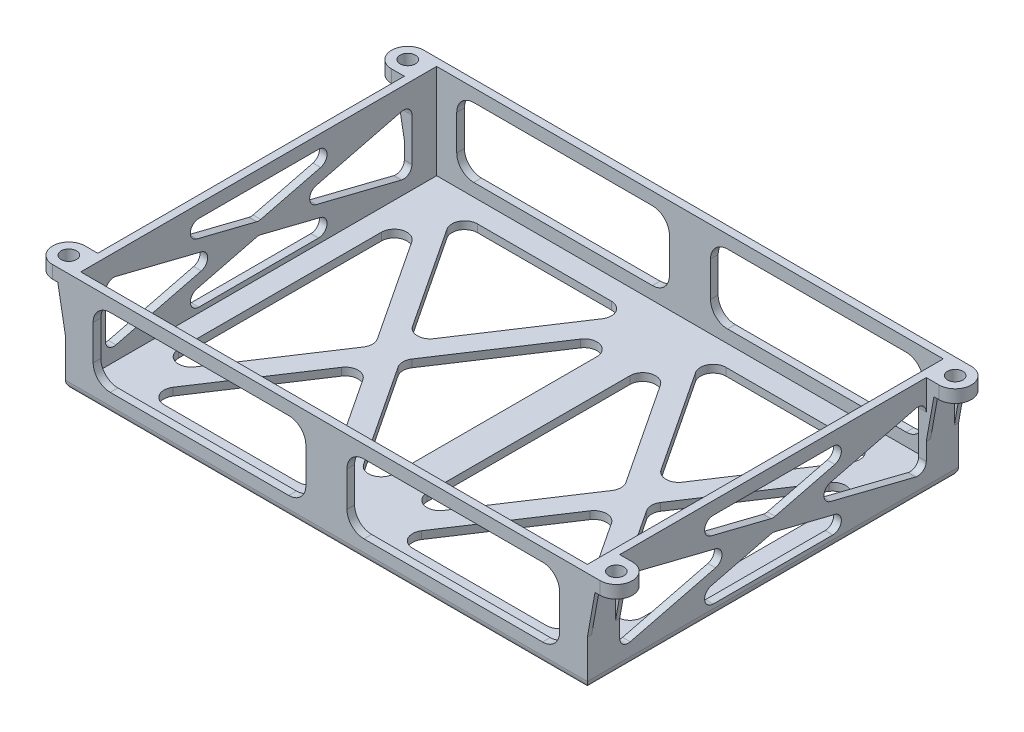
SolidWorks part; units mm, degrees
other "Markup2"
sketch "Sketch32" plane through (-159.4724, 0, 108) normal (-0.262, -0.0774, 0.962) x (0.8638, -0.4632, 0.198)
ref_plane "Front Plane" through (0, 0, 0) normal (0, 0, 1) x (1, 0, 0)
ref_plane "Top Plane" through (0, 0, 0) normal (0, 1, 0) x (1, 0, 0)
ref_plane "Right Plane" through (0, 0, 0) normal (1, 0, 0) x (0, 0, -1)
sketch "Sketch1" plane through (0, 0, 0) normal (0, 1, 0) x (1, 0, 0)
  line L0 (-2.286, -2.286) -> (-2.286, -108.556) construction
  line L1 (0, 0) -> (-155.842, 0)
  line L2 (0, 0) -> (0, -110.842)
  line L3 (0, -110.842) -> (-155.842, -110.842)
  line L4 (-155.842, 0) -> (-155.842, -110.842)
  line L5 (-2.286, -108.556) -> (-153.556, -108.556) construction
  line L6 (-153.556, -2.286) -> (-153.556, -108.556) construction
  line L7 (-2.286, -2.286) -> (-153.556, -2.286) construction
  dimension "D1" = 2.286
  dimension "D2" = 106.27
  dimension "D3" = 151.27
extrude "Boss-Extrude1" add sketch "Sketch1" along normal blind 30.556 contours L1 L4 L3 L2
shell "Shell1" thickness 2.286 removed face at (-77.921, 30.556, 55.421)
sketch "Sketch7" plane through (0, 30.556, 0) normal (0, 1, 0) x (1, 0, 0)
  line L0 (-159.652, 0) -> (-155.842, 0)
  line L1 (-155.842, 0) -> (-155.842, -9.652)
  line L2 (-155.842, 0) -> (-155.842, -110.842) construction
  line L3 (-155.842, -9.652) -> (-159.652, -9.652)
  line L4 (-77.921, -1000) -> (-77.921, 49000) construction
  line L5 (0, 0) -> (-155.842, 0) construction
  line L6 (-1150, -55.421) -> (48850, -55.421) construction
  line L7 (-153.556, -2.286) -> (-153.556, -108.556) construction
  line L8 (-155.842, -101.19) -> (-159.652, -101.19)
  line L9 (-155.842, -110.842) -> (-155.842, -101.19)
  line L10 (-159.652, -110.842) -> (-155.842, -110.842)
  line L11 (3.81, -110.842) -> (0, -110.842)
  line L12 (0, -110.842) -> (0, -101.19)
  line L13 (0, -101.19) -> (3.81, -101.19)
  line L14 (0, -9.652) -> (3.81, -9.652)
  line L15 (0, 0) -> (0, -9.652)
  line L16 (3.81, 0) -> (0, 0)
  circle A0 centre (-159.652, -4.826) radius 2.286
  arc A2 (-159.652, 0) -> (-159.652, -9.652) centre (-159.652, -4.826) ccw
  arc A3 (-159.652, -110.842) -> (-159.652, -101.19) centre (-159.652, -106.016) cw
  circle A4 centre (-159.652, -106.016) radius 2.286
  circle A5 centre (3.81, -106.016) radius 2.286
  arc A6 (3.81, -110.842) -> (3.81, -101.19) centre (3.81, -106.016) ccw
  arc A7 (3.81, 0) -> (3.81, -9.652) centre (3.81, -4.826) cw
  circle A8 centre (3.81, -4.826) radius 2.286
  point P14 (-77.921, 0)
  point P19 (-153.556, -55.421)
  dimension "D1" = 2.54
  dimension "D3" = 4.572
  dimension "D2" = 3.81
extrude "Boss-Extrude7" add sketch "Sketch7" against normal blind 3.81
ref_plane "Plane1" through (0, 0, 55.421) normal (0, 0, -1) x (-1, 0, 0)
ref_plane "Plane2" through (-77.921, 0, 0) normal (-1, 0, 0) x (0, 0, 1)
sketch "Sketch33" plane through (0, 0, 0) normal (1, 0, 0) x (0, 0, -1)
  line L0 (-9.652, 26.746) -> (-101.19, 3.81) construction
  line L1 (-9.652, 26.746) -> (-101.19, 26.746)
  line L2 (-9.652, 26.746) -> (-9.652, 3.81)
  line L3 (-9.652, 3.81) -> (-101.19, 3.81)
  line L4 (-101.19, 26.746) -> (-101.19, 3.81)
  line L5 (-9.652, 3.81) -> (-101.19, 26.746) construction
  line L6 (-9.652, 26.746) -> (-9.652, 30.556) construction
  line L7 (-55.421, 17.111) -> (-93.8746, 26.746)
  line L8 (-9.652, 30.556) -> (-101.19, 30.556) construction
  line L10 (0, 26.746) -> (-9.652, 26.746) construction
  line L11 (-55.421, 13.445) -> (-93.8746, 3.81)
  line L12 (0, 0) -> (-110.842, 0) construction
  line L13 (-9.652, 5.643) -> (-48.1056, 15.278)
  line L14 (-16.9674, 26.746) -> (-55.421, 17.111)
  line L15 (-16.9674, 3.81) -> (-55.421, 13.445)
  line L16 (-9.652, 24.913) -> (-48.1056, 15.278)
  line L17 (-9.2199, 25.0213) -> (-100.7579, 2.0853) construction
  line L18 (-10.0841, 28.4707) -> (-101.6221, 5.5347) construction
  line L19 (-9.2199, 5.5347) -> (-100.7579, 28.4707) construction
  line L20 (-10.0841, 2.0853) -> (-101.6221, 25.0213) construction
  line L21 (-62.7364, 15.278) -> (-101.19, 5.643)
  line L22 (-62.7364, 15.278) -> (-101.19, 24.913)
  point P10 (-55.421, 30.556)
  point P12 (-55.421, 26.746)
  dimension "D1" = 3.81
  dimension "D2" = 1.778
  dimension "D3" = 1.778
extrude "Cut-Extrude1" cut sketch "Sketch33" against normal up to surface (2.286 mm away) contours L3 L15 L11 | L2 L16 L13 | L21 L22 L4 | L14 L1 L7 region at (0, 23.5343, 55.421) region at (0, 15.278, 22.4699) region at (0, 15.278, 88.3721) region at (0, 7.0217, 55.421) up to face at (-2.286, 16.421, 55.421)
fillet "Fillet1" radius 2.54 12 edges at (-1.143, 3.81, 16.9674) (-1.143, 13.445, 55.421) (-1.143, 3.81, 93.8746) (-1.143, 5.643, 101.19) (-1.143, 24.913, 101.19) (-1.143, 15.278, 62.7364) (-1.143, 17.111, 55.421) (-1.143, 26.746, 93.8746) (-1.143, 26.746, 16.9674) (-1.143, 5.643, 9.652) (-1.143, 24.913, 9.652) (-1.143, 15.278, 48.1056)
mirror "Mirror1" about plane through (-77.921, 0, 0) normal (-1, 0, 0) of "Fillet1", "Cut-Extrude1"
sketch "Sketch34" plane through (0, 0, 108.556) normal (0, 0, -1) x (-1, 0, 0)
  line L0 (84.056, 16.421) -> (71.786, 16.421) construction
  line L1 (142.476, 6.096) -> (89.136, 6.096)
  line L2 (147.556, 11.176) -> (147.556, 21.666)
  line L3 (142.476, 26.746) -> (89.136, 26.746)
  line L4 (84.056, 11.176) -> (84.056, 21.666)
  line L5 (66.706, 6.096) -> (13.366, 6.096)
  line L6 (71.786, 11.176) -> (71.786, 21.666)
  line L7 (66.706, 26.746) -> (13.366, 26.746)
  line L8 (8.286, 11.176) -> (8.286, 21.666)
  line L9 (2.286, 30.556) -> (153.556, 30.556) construction
  line L10 (153.556, 30.556) -> (153.556, 2.286) construction
  line L11 (2.286, 2.286) -> (153.556, 2.286) construction
  arc A0 (142.476, 6.096) -> (147.556, 11.176) centre (142.476, 11.176) ccw
  arc A1 (147.556, 21.666) -> (142.476, 26.746) centre (142.476, 21.666) ccw
  arc A2 (89.136, 26.746) -> (84.056, 21.666) centre (89.136, 21.666) ccw
  arc A3 (89.136, 6.096) -> (84.056, 11.176) centre (89.136, 11.176) cw
  arc A4 (13.366, 6.096) -> (8.286, 11.176) centre (13.366, 11.176) cw
  arc A5 (66.706, 6.096) -> (71.786, 11.176) centre (66.706, 11.176) ccw
  arc A6 (71.786, 21.666) -> (66.706, 26.746) centre (66.706, 21.666) ccw
  arc A7 (13.366, 26.746) -> (8.286, 21.666) centre (13.366, 21.666) ccw
  point P12 (77.921, 30.556)
  point P13 (77.921, 16.421)
  point P16 (153.556, 16.421)
  point P17 (147.556, 16.421)
  point P30 (8.286, 6.096)
  point P33 (71.786, 6.096)
  dimension "D4" = 5.08
  dimension "D1" = 6
  dimension "D2" = 63.5
  dimension "D3" = 3.81
extrude "Cut-Extrude2" cut sketch "Sketch34" against normal through all both and the other way through all
fillet "Fillet2" radius 2.54 4 edges at (-77.921, 0, 0) (-155.842, 0, 55.421) (-77.921, 0, 110.842) (0, 0, 55.421)
sketch "Sketch36" plane through (0, 2.286, 0) normal (0, 1, 0) x (1, 0, 0)
  line L0 (-95.0296, -8.636) -> (-135.0264, -8.636)
  line L2 (-155.842, 0) -> (-155.842, -110.842) construction
  line L4 (-143.396, -98.396) -> (-86.66, -12.446) construction
  line L6 (-82.85, -85.7168) -> (-82.85, -25.1252)
  line L7 (-143.396, -12.446) -> (-86.66, -98.396) construction
  line L9 (0, 0) -> (-155.842, 0) construction
  line L11 (-155.842, -110.842) -> (0, -110.842) construction
  line L14 (-147.206, -25.1252) -> (-147.206, -85.7168)
  line L15 (-135.0264, -102.206) -> (-95.0296, -102.206)
  line L16 (-147.2575, -104.2459) -> (-85.5486, -10.7623) construction
  line L17 (-77.921, -1089.6267) -> (-77.921, 48910.3733) construction
  line L18 (-140.2163, -23.0262) -> (-120.2179, -53.3221)
  line L19 (-138.2061, -96.2971) -> (-118.2077, -66.0012)
  line L22 (-138.2061, -14.5449) -> (-118.2077, -44.8408)
  line L23 (-140.2163, -87.8158) -> (-120.2179, -57.5199)
  line L26 (-140.7462, -10.6969) -> (-84.0102, -96.6469) construction
  line L27 (-146.0458, -14.1951) -> (-89.3098, -100.1451) construction
  line L28 (-144.6078, -105.995) -> (-82.8989, -12.5115) construction
  line L29 (-149.9073, -102.4967) -> (-88.1984, -9.0132) construction
  line L30 (-2.54, -108.302) -> (-153.302, -108.302) construction
  line L31 (-12.446, -12.446) -> (-69.182, -98.396) construction
  line L32 (-12.446, -98.396) -> (-69.182, -12.446) construction
  line L33 (-43.9937, -44.8408) -> (-63.9921, -14.5449)
  line L38 (-109.8381, -53.3221) -> (-89.8397, -23.0262)
  line L39 (-109.8381, -57.5199) -> (-89.8397, -87.8158)
  line L40 (-111.8483, -66.0012) -> (-91.8499, -96.2971)
  line L41 (-111.8483, -44.8408) -> (-91.8499, -14.5449)
  line L42 (-43.9937, -66.0012) -> (-63.9921, -96.2971)
  line L43 (-46.0039, -57.5199) -> (-66.0023, -87.8158)
  line L44 (-46.0039, -53.3221) -> (-66.0023, -23.0262)
  line L45 (-15.6257, -87.8158) -> (-35.6241, -57.5199)
  line L46 (-17.6359, -14.5449) -> (-37.6343, -44.8408)
  line L47 (-17.6359, -96.2971) -> (-37.6343, -66.0012)
  line L48 (-15.6257, -23.0262) -> (-35.6241, -53.3221)
  line L49 (-20.8156, -102.206) -> (-60.8124, -102.206)
  line L50 (-8.636, -25.1252) -> (-8.636, -85.7168)
  line L51 (-72.992, -85.7168) -> (-72.992, -25.1252)
  line L52 (-60.8124, -8.636) -> (-20.8156, -8.636)
  arc A12 (-138.2061, -14.5449) -> (-135.0264, -8.636) centre (-135.0264, -12.446) cw
  arc A13 (-91.8499, -14.5449) -> (-95.0296, -8.636) centre (-95.0296, -12.446) ccw
  arc A14 (-89.8397, -23.0262) -> (-82.85, -25.1252) centre (-86.66, -25.1252) cw
  arc A15 (-109.8381, -53.3221) -> (-109.8381, -57.5199) centre (-106.6584, -55.421) ccw
  arc A16 (-89.8397, -87.8158) -> (-82.85, -85.7168) centre (-86.66, -85.7168) ccw
  arc A17 (-118.2077, -66.0012) -> (-111.8483, -66.0012) centre (-115.028, -68.1002) cw
  arc A18 (-91.8499, -96.2971) -> (-95.0296, -102.206) centre (-95.0296, -98.396) cw
  arc A19 (-138.2061, -96.2971) -> (-135.0264, -102.206) centre (-135.0264, -98.396) ccw
  arc A20 (-140.2163, -87.8158) -> (-147.206, -85.7168) centre (-143.396, -85.7168) cw
  arc A21 (-120.2179, -53.3221) -> (-120.2179, -57.5199) centre (-123.3976, -55.421) cw
  arc A22 (-140.2163, -23.0262) -> (-147.206, -25.1252) centre (-143.396, -25.1252) ccw
  arc A23 (-111.8483, -44.8408) -> (-118.2077, -44.8408) centre (-115.028, -42.7418) cw
  arc A24 (-43.9937, -44.8408) -> (-37.6343, -44.8408) centre (-40.814, -42.7418) ccw
  arc A25 (-15.6257, -23.0262) -> (-8.636, -25.1252) centre (-12.446, -25.1252) cw
  arc A26 (-35.6241, -53.3221) -> (-35.6241, -57.5199) centre (-32.4444, -55.421) ccw
  arc A27 (-15.6257, -87.8158) -> (-8.636, -85.7168) centre (-12.446, -85.7168) ccw
  arc A28 (-17.6359, -96.2971) -> (-20.8156, -102.206) centre (-20.8156, -98.396) cw
  arc A29 (-63.9921, -96.2971) -> (-60.8124, -102.206) centre (-60.8124, -98.396) ccw
  arc A30 (-37.6343, -66.0012) -> (-43.9937, -66.0012) centre (-40.814, -68.1002) ccw
  arc A31 (-66.0023, -87.8158) -> (-72.992, -85.7168) centre (-69.182, -85.7168) cw
  arc A32 (-46.0039, -53.3221) -> (-46.0039, -57.5199) centre (-49.1836, -55.421) cw
  arc A33 (-66.0023, -23.0262) -> (-72.992, -25.1252) centre (-69.182, -25.1252) ccw
  arc A34 (-63.9921, -14.5449) -> (-60.8124, -8.636) centre (-60.8124, -12.446) cw
  arc A35 (-17.6359, -14.5449) -> (-20.8156, -8.636) centre (-20.8156, -12.446) ccw
  point P18 (-77.921, -108.302)
  point P87 (-111.2236, -55.421)
  point P90 (-82.85, -98.4045)
  point P93 (-115.028, -61.1843)
  point P96 (-87.9494, -102.206)
  point P99 (-142.1066, -102.206)
  point P102 (-147.206, -98.4045)
  point P107 (-8.636, -98.4045)
  point P108 (-13.7354, -102.206)
  point P109 (-67.8926, -102.206)
  point P110 (-40.814, -61.1843)
  point P111 (-72.992, -98.4045)
  point P112 (-44.6184, -55.421)
  dimension "D8" = 3.81
  dimension "D7" = 3.81
  dimension "D2" = 8.636
  dimension "D3" = 3.175
  dimension "D5" = 8.636
  dimension "D6" = 72.992
  dimension "D1" = 8.636
  dimension "D4" = 3.175
extrude "Cut-Extrude3" cut sketch "Sketch36" against normal through all
sketch "Sketch39" plane through (0, 0, 0) normal (0, 0, -1) x (-1, 0, 0)
  line L0 (158.128, 26.746) -> (155.842, 14.046)
  line L1 (155.842, 26.746) -> (155.842, 2.54) construction
  line L3 (155.842, 26.746) -> (159.652, 26.746) construction
  dimension "D1" = 12.7
  dimension "D2" = 2.286
sketch "Sketch40" plane through (0, 0, 9.652) normal (0, 0, 1) x (1, 0, 0)
  line L0 (-158.128, 26.746) -> (-155.842, 14.046) construction
  line L1 (-158.128, 26.746) -> (-155.842, 14.046)
rib "Rib1" sketch "Sketch40" sketch "Sketch40" thickness 1.27 extrusion direction parallel to sketch draft on no parameters "D1"=1.27
rib "Rib2" sketch "Sketch39" sketch "Sketch39" thickness 1.27 extrusion direction parallel to sketch draft on no parameters "D1"=1.27
mirror "Mirror2" about plane through (0, 0, 55.421) normal (0, 0, -1) of "Rib1", "Rib2"
mirror "Mirror3" about plane through (-77.921, 0, 0) normal (-1, 0, 0) of "Mirror2"
